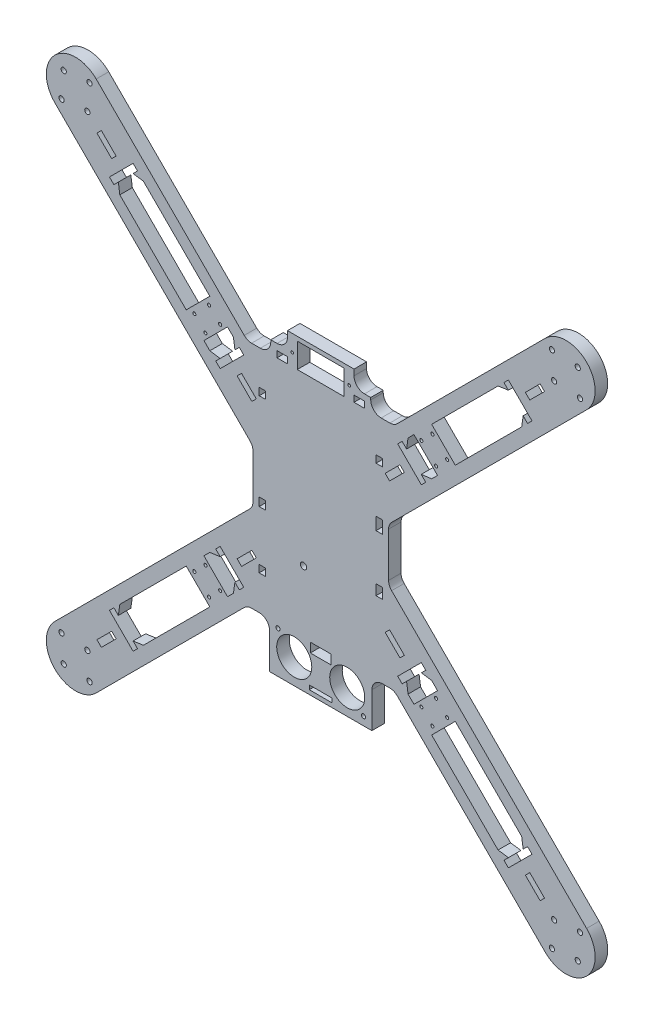
SolidWorks part; units mm, degrees
material "Custom Plastic"
ref_plane "Front Plane" through (0, 0, 0) normal (0, 0, 1) x (1, 0, 0)
ref_plane "Top Plane" through (0, 0, 0) normal (0, 1, 0) x (1, 0, 0)
ref_plane "Right Plane" through (0, 0, 0) normal (1, 0, 0) x (0, 0, -1)
sketch "Sketch1" plane through (0, 0, 0) normal (0, 0, 1) x (1, 0, 0)
  line L0 (117.5, 117.5) -> (-117.5, 117.5) construction
  line L1 (-117.5, 117.5) -> (117.5, -117.5) construction
  line L2 (117.5, -117.5) -> (-117.5, -117.5) construction
  line L3 (-117.5, -117.5) -> (117.5, 117.5) construction
  line L4 (117.5, 117.5) -> (117.5, -117.5) construction
  line L5 (-117.5, 117.5) -> (-117.5, -117.5) construction
  line L6 (0, 117.5) -> (0, -117.5) construction
  line L7 (35.201, 55) -> (15.95, 55)
  line L8 (-32.5, 55) -> (32.5, 55) construction
  line L9 (-35.201, 55) -> (-107.6005, 127.3995)
  line L10 (-127.3995, 107.6005) -> (-32.5, 12.701)
  line L11 (-117.5, 0) -> (117.5, 0) construction
  line L12 (-32.5, 12.701) -> (-32.5, -12.701)
  line L13 (32.5, 55) -> (32.5, -55) construction
  line L14 (32.5, -55) -> (-32.5, -55) construction
  line L15 (-32.5, -55) -> (-32.5, 55) construction
  line L16 (32.5, 55) -> (-32.5, -55) construction
  line L17 (-24.5, -55) -> (-24.5, -77)
  line L18 (-127.3995, -107.6005) -> (-32.5, -12.701)
  line L19 (-24.5, -77) -> (24.5, -77)
  line L20 (-35.201, -55) -> (-107.6005, -127.3995)
  line L21 (35.201, -55) -> (24.5, -55)
  line L22 (35.201, -55) -> (107.6005, -127.3995)
  line L23 (127.3995, -107.6005) -> (32.5, -12.701)
  line L24 (32.5, 12.701) -> (32.5, -12.701)
  line L25 (127.3995, 107.6005) -> (32.5, 12.701)
  line L26 (35.201, 55) -> (107.6005, 127.3995)
  line L27 (24.5, -55) -> (24.5, -77)
  line L28 (-24.5, -55) -> (-35.201, -55)
  line L29 (-15.95, 55) -> (-15.95, 68.8)
  line L30 (-15.95, 68.8) -> (15.95, 68.8)
  line L31 (15.95, 55) -> (15.95, 68.8)
  line L32 (-15.95, 55) -> (-35.201, 55)
  arc A0 (-107.6005, 127.3995) -> (-127.3995, 107.6005) centre (-117.5, 117.5) ccw
  arc A12 (-107.6005, -127.3995) -> (-127.3995, -107.6005) centre (-117.5, -117.5) cw
  arc A16 (107.6005, -127.3995) -> (127.3995, -107.6005) centre (117.5, -117.5) ccw
  arc A24 (107.6005, 127.3995) -> (127.3995, 107.6005) centre (117.5, 117.5) cw
  point P3 (0, 0)
  point P18 (0, 0)
  point P21 (0, -77)
  point P26 (0, 68.8)
  point P33 (-117.5, 117.5)
  point P34 (-32.5, 0)
  point P65 (0, -55)
  point P80 (0, 55)
  dimension "D3" = 14
  dimension "D8" = 24.5
  dimension "D7" = 22
  dimension "D1" = 235
  dimension "D2" = 235
  dimension "D4" = 65
  dimension "D5" = 110
  dimension "D6" = 28
  dimension "D9" = 13.8
  dimension "D10" = 31.9
extrude "Boss-Extrude1" add sketch "Sketch1" against normal blind 6
sketch "Sketch4" plane through (0, 0, 0) normal (0, 0, 1) x (1, 0, 0)
  line L0 (0, 0) -> (0, 55) construction
  line L2 (0, 0) -> (-32.5, 0) construction
  line L3 (-32.5, 12.701) -> (-32.5, -12.701) construction
  line L4 (-32.5, 0) -> (-32.5, 12.701) construction
  line L5 (-32.5, 12.701) -> (-127.3995, 107.6005) construction
  line L6 (-35.201, 55) -> (-107.6005, 127.3995) construction
  line L7 (-107.6005, 127.3995) -> (-127.3995, 107.6005) construction
  line L8 (-110.7825, 124.2175) -> (-124.2175, 110.7825) construction
  line L9 (-123.1569, 123.1569) -> (-111.8431, 111.8431) construction
  circle A20 centre (-110.7825, 124.2175) radius 1.25
  circle A21 centre (-124.2175, 110.7825) radius 1.25
  circle A22 centre (-123.1569, 123.1569) radius 1.25
  circle A23 centre (-111.8431, 111.8431) radius 1.25
  circle A24 centre (111.8431, 111.8431) radius 1.25
  circle A25 centre (110.7825, 124.2175) radius 1.25
  circle A26 centre (123.1569, 123.1569) radius 1.25
  circle A27 centre (124.2175, 110.7825) radius 1.25
  circle A28 centre (111.8431, -111.8431) radius 1.25
  circle A29 centre (124.2175, -110.7825) radius 1.25
  circle A30 centre (123.1569, -123.1569) radius 1.25
  circle A31 centre (110.7825, -124.2175) radius 1.25
  circle A32 centre (-111.8431, -111.8431) radius 1.25
  circle A33 centre (-110.7825, -124.2175) radius 1.25
  circle A34 centre (-123.1569, -123.1569) radius 1.25
  circle A35 centre (-124.2175, -110.7825) radius 1.25
  point P16 (-117.5, 117.5)
  point P19 (-117.5, 117.5)
  point P26 (-117.5, 117.5)
  point P62 (0, 0)
  dimension "D1" = 55
  dimension "D4" = 2.5
  dimension "D2" = 19
  dimension "D5" = 35.201
  dimension "D3" = 16
extrude "Cut-Extrude1" cut sketch "Sketch4" against normal through all
sketch "Sketch5" plane through (0, 0, 0) normal (0, 0, 1) x (1, 0, 0)
  line L4 (0, 0) -> (0, 14.0392) construction
  line L6 (15.95, 68.8) -> (-15.95, 68.8) construction
  line L7 (-11.25, 66.8) -> (-11.25, 55)
  line L8 (-11.25, 55) -> (11.25, 55)
  line L9 (11.25, 55) -> (11.25, 66.8)
  line L10 (11.25, 66.8) -> (-11.25, 66.8)
  line L12 (0, 66.8) -> (0, 55) construction
  line L13 (-13.65, 60.9) -> (13.65, 60.9) construction
  circle A2 centre (-13.65, 60.9) radius 0.65
  circle A3 centre (13.65, 60.9) radius 0.65
  point P20 (0, 60.9)
  point P21 (0, 60.9)
  dimension "D8" = 1.3
  dimension "D9" = 1.3
  dimension "D2" = 2
  dimension "D10" = 27.3
  dimension "D11" = 22.5
  dimension "D12" = 11.8
extrude "Cut-Extrude2" cut sketch "Sketch5" against normal through all
sketch "Sketch6" plane through (0, 0, 0) normal (0, 0, 1) x (1, 0, 0)
  line L1 (-11.25, 55) -> (11.25, 55) construction
  circle A0 centre (-8.25, -25) radius 1.5
  dimension "D3" = 3
  dimension "D1" = 80
  dimension "D2" = 3
extrude "Cut-Extrude3" cut sketch "Sketch6" against normal through all
sketch "Sketch7" plane through (0, 0, 0) normal (0, 0, 1) x (1, 0, 0)
  line L0 (-22.5, -55) -> (-22.5, -75) construction
  line L5 (-22.5, -75) -> (22.5, -75) construction
  line L6 (22.5, -75) -> (22.5, -55) construction
  line L7 (22.5, -55) -> (-22.5, -55) construction
  line L8 (0, -55) -> (0, -75) construction
  line L9 (-12.7, -65) -> (0, -65) construction
  line L10 (-24.5, -77) -> (24.5, -77) construction
  line L11 (-24.5, -55) -> (-24.5, -77) construction
  line L12 (-5, -55) -> (-5, -59.5)
  line L13 (-5, -59.5) -> (5, -59.5)
  line L15 (5, -55) -> (-5, -55)
  line L16 (-5.5, -75) -> (-5.5, -73)
  line L17 (-5.5, -73) -> (5.5, -73)
  line L21 (5.5, -75) -> (-5.5, -75)
  line L22 (5, -55) -> (5, -59.5)
  line L23 (5.5, -75) -> (5.5, -73)
  circle A5 centre (-20.5, -57) radius 1
  circle A6 centre (-12.7, -65) radius 8.4
  circle A7 centre (12.7, -65) radius 8.4
  circle A8 centre (20.5, -73) radius 1
  point P25 (0, -59.5)
  point P26 (0, -73)
  dimension "D3" = 2
  dimension "D6" = 20
  dimension "D13" = 5.5
  dimension "D5" = 45
  dimension "D1" = 2
  dimension "D4" = 16.8
  dimension "D14" = 2
  dimension "D2" = 2
  dimension "D7" = 2
  dimension "D8" = 2
  dimension "D9" = 12.7
  dimension "D10" = 5
  dimension "D11" = 4.5
  dimension "D12" = 2
  dimension "D15" = 2
  dimension "D16" = 2
extrude "Cut-Extrude4" cut sketch "Sketch7" against normal through all
sketch "Sketch8" plane through (0, 0, 0) normal (0, 0, 1) x (1, 0, 0)
  line L0 (101.2365, -89.9228) -> (89.9228, -101.2365)
  line L1 (89.9228, -101.2365) -> (87.8015, -99.1152)
  line L2 (36.8898, -48.2035) -> (48.2035, -36.8898)
  line L3 (48.2035, -36.8898) -> (50.3249, -39.0111)
  line L4 (105.4792, -85.6802) -> (85.6802, -105.4792) construction
  line L5 (127.3995, -107.6005) -> (32.5, -12.701) construction
  line L6 (35.201, -55) -> (107.6005, -127.3995) construction
  line L7 (40.0718, -37.9505) -> (37.9505, -40.0718)
  line L8 (115.8431, -107.8431) -> (111.8431, -111.8431) construction
  line L9 (37.9505, -40.0718) -> (30.8794, -33.0007)
  line L10 (50.3249, 39.0111) -> (48.2035, 36.8898)
  line L11 (30.8794, -33.0007) -> (33.0007, -30.8794)
  line L12 (33.0007, -30.8794) -> (40.0718, -37.9505)
  line L13 (42.5467, -42.5467) -> (39.0111, -39.0111) construction
  line L14 (35.201, -55) -> (107.6005, -127.3995) construction
  line L15 (100.1759, -98.0546) -> (98.0546, -100.1759)
  line L16 (98.0546, -100.1759) -> (105.1256, -107.247)
  line L17 (105.1256, -107.247) -> (107.247, -105.1256)
  line L18 (107.247, -105.1256) -> (100.1759, -98.0546)
  line L19 (99.1152, -99.1152) -> (95.5797, -95.5797) construction
  line L20 (-101.2365, -89.9228) -> (-99.1152, -87.8015)
  line L21 (-100.1759, -98.0546) -> (-107.247, -105.1256)
  line L22 (-107.247, -105.1256) -> (-105.1256, -107.247)
  line L23 (-105.1256, -107.247) -> (-98.0546, -100.1759)
  line L24 (-98.0546, -100.1759) -> (-100.1759, -98.0546)
  line L25 (-89.9228, -101.2365) -> (-101.2365, -89.9228)
  line L26 (-36.8898, -48.2035) -> (-39.0111, -50.3249)
  line L27 (-48.2035, -36.8898) -> (-36.8898, -48.2035)
  line L28 (-37.9505, -40.0718) -> (-40.0718, -37.9505)
  line L29 (-30.8794, -33.0007) -> (-37.9505, -40.0718)
  line L30 (-40.0718, -37.9505) -> (-33.0007, -30.8794)
  line L31 (-33.0007, -30.8794) -> (-30.8794, -33.0007)
  line L32 (-89.9228, 101.2365) -> (-87.8015, 99.1152)
  line L33 (-98.0546, 100.1759) -> (-105.1256, 107.247)
  line L34 (-105.1256, 107.247) -> (-107.247, 105.1256)
  line L35 (-107.247, 105.1256) -> (-100.1759, 98.0546)
  line L36 (-100.1759, 98.0546) -> (-98.0546, 100.1759)
  line L37 (-101.2365, 89.9228) -> (-89.9228, 101.2365)
  line L38 (-48.2035, 36.8898) -> (-50.3249, 39.0111)
  line L39 (-36.8898, 48.2035) -> (-48.2035, 36.8898)
  line L40 (-40.0718, 37.9505) -> (-37.9505, 40.0718)
  line L41 (-33.0007, 30.8794) -> (-40.0718, 37.9505)
  line L42 (-37.9505, 40.0718) -> (-30.8794, 33.0007)
  line L43 (-30.8794, 33.0007) -> (-33.0007, 30.8794)
  line L44 (101.2365, 89.9228) -> (99.1152, 87.8015)
  line L45 (100.1759, 98.0546) -> (107.247, 105.1256)
  line L46 (107.247, 105.1256) -> (105.1256, 107.247)
  line L47 (105.1256, 107.247) -> (98.0546, 100.1759)
  line L48 (98.0546, 100.1759) -> (100.1759, 98.0546)
  line L49 (89.9228, 101.2365) -> (101.2365, 89.9228)
  line L50 (36.8898, 48.2035) -> (39.0111, 50.3249)
  line L51 (48.2035, 36.8898) -> (36.8898, 48.2035)
  line L52 (37.9505, 40.0718) -> (40.0718, 37.9505)
  line L53 (30.8794, 33.0007) -> (37.9505, 40.0718)
  line L54 (40.0718, 37.9505) -> (33.0007, 30.8794)
  line L55 (33.0007, 30.8794) -> (30.8794, 33.0007)
  line L56 (32.5, 12.701) -> (127.3995, 107.6005) construction
  line L57 (41.8396, 53.1533) -> (84.9731, 96.2868)
  line L58 (96.2868, 84.9731) -> (53.1533, 41.8396)
  line L59 (87.8015, 99.1152) -> (89.9228, 101.2365)
  line L60 (99.1152, -87.8015) -> (96.9939, -89.9228)
  line L61 (-96.2868, -84.9731) -> (-53.1533, -41.8396)
  line L62 (96.9939, -89.9228) -> (96.2868, -84.9731)
  line L63 (99.1152, -87.8015) -> (101.2365, -89.9228)
  line L64 (87.8015, -99.1152) -> (89.9228, -96.9939)
  line L65 (-87.8015, -99.1152) -> (-89.9228, -101.2365)
  line L66 (89.9228, -96.9939) -> (84.9731, -96.2868)
  line L67 (84.9731, -96.2868) -> (41.8396, -53.1533)
  line L68 (50.3249, -39.0111) -> (48.2035, -41.1325)
  line L69 (48.2035, -41.1325) -> (53.1533, -41.8396)
  line L70 (53.1533, -41.8396) -> (96.2868, -84.9731)
  line L71 (39.0111, -50.3249) -> (41.1325, -48.2035)
  line L72 (41.1325, -48.2035) -> (41.8396, -53.1533)
  line L73 (39.0111, -50.3249) -> (36.8898, -48.2035)
  line L74 (-89.9228, -96.9939) -> (-84.9731, -96.2868)
  line L75 (-87.8015, -99.1152) -> (-89.9228, -96.9939)
  line L76 (-96.9939, -89.9228) -> (-96.2868, -84.9731)
  line L77 (-99.1152, -87.8015) -> (-96.9939, -89.9228)
  line L78 (-41.1325, -48.2035) -> (-41.8396, -53.1533)
  line L79 (-39.0111, -50.3249) -> (-41.1325, -48.2035)
  line L80 (-48.2035, -41.1325) -> (-53.1533, -41.8396)
  line L81 (-50.3249, -39.0111) -> (-48.2035, -41.1325)
  line L82 (-96.9939, 89.9228) -> (-96.2868, 84.9731)
  line L83 (-99.1152, 87.8015) -> (-96.9939, 89.9228)
  line L84 (-89.9228, 96.9939) -> (-84.9731, 96.2868)
  line L85 (-87.8015, 99.1152) -> (-89.9228, 96.9939)
  line L86 (-48.2035, 41.1325) -> (-53.1533, 41.8396)
  line L87 (-50.3249, 39.0111) -> (-48.2035, 41.1325)
  line L88 (-41.1325, 48.2035) -> (-41.8396, 53.1533)
  line L89 (-39.0111, 50.3249) -> (-41.1325, 48.2035)
  line L90 (89.9228, 96.9939) -> (84.9731, 96.2868)
  line L91 (87.8015, 99.1152) -> (89.9228, 96.9939)
  line L92 (96.9939, 89.9228) -> (96.2868, 84.9731)
  line L93 (99.1152, 87.8015) -> (96.9939, 89.9228)
  line L94 (41.1325, 48.2035) -> (41.8396, 53.1533)
  line L95 (39.0111, 50.3249) -> (41.1325, 48.2035)
  line L96 (48.1429, 41.1931) -> (53.1533, 41.8396)
  line L97 (50.3249, 39.0111) -> (48.1429, 41.1931)
  line L98 (-39.0111, 50.3249) -> (-36.8898, 48.2035)
  line L99 (-53.1533, 41.8396) -> (-96.2868, 84.9731)
  line L100 (-99.1152, 87.8015) -> (-101.2365, 89.9228)
  line L101 (-84.9731, 96.2868) -> (-41.8396, 53.1533)
  line L102 (-41.8396, -53.1533) -> (-84.9731, -96.2868)
  line L103 (-50.3249, -39.0111) -> (-48.2035, -36.8898)
  line L104 (96.2868, 84.9731) -> (84.9731, 96.2868) construction
  line L105 (53.1533, 41.8396) -> (41.8396, 53.1533) construction
  point P10 (95.5797, -95.5797)
  point P11 (95.5797, -95.5797)
  point P18 (-49.2642, 40.0718)
  point P19 (-49.2642, -40.0718)
  point P68 (0, 0)
  point P122 (0, 0)
  dimension "D1" = 23
  dimension "D2" = 75
  dimension "D3" = 3
  dimension "D4" = 10
  dimension "D5" = 5
  dimension "D6" = 6
  dimension "D7" = 3
  dimension "D8" = 10
  dimension "D9" = 5
  dimension "D11" = 6
  dimension "D12" = 3
  dimension "D13" = 4
  dimension "D14" = 3
  dimension "D15" = 3
  dimension "D16" = 4
  dimension "D17" = 3
  dimension "D18" = 3
  dimension "D19" = 4
  dimension "D20" = 3
  dimension "D21" = 3
  dimension "D22" = 4
  dimension "D23" = 3
  dimension "D24" = 3
  dimension "D25" = 4
  dimension "D26" = 3
  dimension "D27" = 4
  dimension "D28" = 3
  dimension "D29" = 3
  dimension "D30" = 4
  dimension "D31" = 4
  dimension "D32" = 3
  dimension "D33" = 3
  dimension "D34" = 4
  dimension "D35" = 4
  dimension "D36" = 3
  dimension "D37" = 3
  dimension "D38" = 4
  dimension "D39" = 4
  dimension "D40" = 3
  dimension "D41" = 3
  dimension "D42" = 4
  dimension "D43" = 4
  dimension "D10" = 4
extrude "Cut-Extrude5" cut sketch "Sketch8" against normal through all
sketch "Sketch9" plane through (-5.6569, 5.6569, 0) normal (0.7071, -0.7071, 0) x (0, 0, -1)
  line L0 (6, 128.1701) -> (6, 67.1701) construction
  line L1 (6, 83.1701) -> (0, 83.1701)
  line L2 (6, 83.1701) -> (6, 71.1701)
  line L3 (6, 71.1701) -> (0, 71.1701)
  line L4 (0, 83.1701) -> (0, 71.1701)
  line L5 (0, 128.1701) -> (0, 67.1701) construction
  line L6 (0, 0) -> (28.0274, 0) construction
  line L7 (6, 63.1701) -> (0, 63.1701) construction
  dimension "D1" = 8
  dimension "D2" = 12
extrude "Boss-Extrude2" add sketch "Sketch9" along normal up to next
sketch "Sketch11" plane through (5.6569, 5.6569, 0) normal (-0.7071, -0.7071, 0) x (0, 0, 1)
  line L0 (-6, -128.1701) -> (-6, -67.1701) construction
  line L1 (-6, -71.1701) -> (0, -71.1701)
  line L2 (-6, -71.1701) -> (-6, -83.1701)
  line L3 (-6, -83.1701) -> (0, -83.1701)
  line L4 (0, -71.1701) -> (0, -83.1701)
  line L5 (0, -128.1701) -> (0, -67.1701) construction
  line L6 (-6, -63.1701) -> (0, -63.1701) construction
  dimension "D1" = 8
  dimension "D2" = 12
extrude "Boss-Extrude3" add sketch "Sketch11" along normal up to next
sketch "Sketch12" plane through (5.6569, -5.6569, 0) normal (-0.7071, 0.7071, 0) x (0, 0, 1)
  line L0 (-6, -128.1701) -> (-6, -67.1701) construction
  line L1 (-6, -71.1701) -> (0, -71.1701)
  line L2 (-6, -71.1701) -> (-6, -83.1701)
  line L3 (-6, -83.1701) -> (0, -83.1701)
  line L4 (0, -71.1701) -> (0, -83.1701)
  line L5 (0, -128.1701) -> (0, -67.1701) construction
  dimension "D1" = 8
  dimension "D2" = 12
extrude "Boss-Extrude4" add sketch "Sketch12" along normal up to next
sketch "Sketch13" plane through (5.6569, 5.6569, 0) normal (-0.7071, -0.7071, 0) x (0, 0, 1)
  line L0 (-6, 67.1701) -> (-6, 128.1701) construction
  line L1 (-6, 71.1701) -> (0, 71.1701)
  line L2 (-6, 71.1701) -> (-6, 83.1701)
  line L3 (-6, 83.1701) -> (0, 83.1701)
  line L4 (0, 71.1701) -> (0, 83.1701)
  line L5 (0, 67.1701) -> (0, 128.1701) construction
  dimension "D1" = 8
  dimension "D2" = 12
extrude "Boss-Extrude5" add sketch "Sketch13" along normal up to next
sketch "Sketch14" plane through (0, 0, -6) normal (0, 0, -1) x (-1, 0, 0)
  line L0 (32.5, 0) -> (-32.5, 0) construction
  line L1 (32.5, 12.701) -> (32.5, -12.701) construction
  line L2 (-32.5, -12.701) -> (-32.5, 12.701) construction
  line L3 (28, -38.5) -> (28, 38.5) construction
  line L14 (-26.5, 13) -> (-26.5, 7)
  line L17 (-26.5, 7) -> (-29.5, 7)
  line L19 (-26.5, 13) -> (-29.5, 13)
  line L23 (26.5, -38.5) -> (29.5, -38.5)
  line L24 (26.5, -38.5) -> (26.5, -35)
  line L25 (26.5, -35) -> (29.5, -35)
  line L26 (29.5, -38.5) -> (29.5, -35)
  line L27 (26.5, -11) -> (29.5, -11)
  line L28 (26.5, -11) -> (26.5, -7)
  line L29 (26.5, -7) -> (29.5, -7)
  line L30 (29.5, -11) -> (29.5, -7)
  line L31 (26.5, 35) -> (29.5, 35)
  line L32 (26.5, 35) -> (26.5, 38.5)
  line L33 (26.5, 38.5) -> (29.5, 38.5)
  line L34 (29.5, 35) -> (29.5, 38.5)
  line L35 (-29.5, 13) -> (-29.5, 7)
  line L36 (32.5, 12.701) -> (32.5, -12.701) construction
  line L37 (-26.5, -20) -> (-29.5, -20)
  line L38 (-26.5, -20) -> (-26.5, -15)
  line L39 (-26.5, -15) -> (-29.5, -15)
  line L40 (-29.5, -20) -> (-29.5, -15)
  line L41 (-26.5, 35) -> (-29.5, 35)
  line L42 (-26.5, 35) -> (-26.5, 38.5)
  line L43 (-26.5, 38.5) -> (-29.5, 38.5)
  line L44 (-29.5, 35) -> (-29.5, 38.5)
  line L45 (-32.5, -12.701) -> (-32.5, 12.701) construction
  point P11 (28, -38.5)
  point P16 (28, 0)
  point P28 (-28, 13)
  point P38 (-28, 7)
  dimension "D2" = 3
  dimension "D3" = 3.5
  dimension "D4" = 24
  dimension "D5" = 7
  dimension "D6" = 22
  dimension "D7" = 6
  dimension "D8" = 3.5
  dimension "D9" = 22
  dimension "D10" = 4
  dimension "D11" = 3.5
  dimension "D12" = 42
  dimension "D13" = 5
  dimension "D14" = 3
  dimension "D15" = 3
  dimension "D16" = 3
  dimension "D17" = 7
extrude "Cut-Extrude6" cut sketch "Sketch14" against normal through all
sketch "Sketch15" plane through (0, 0, -6) normal (0, 0, -1) x (-1, 0, 0)
  line L0 (-55.2746, -48.2035) -> (-48.2035, -55.2746) construction
  line L1 (-48.2035, -55.2746) -> (-53.5068, -60.5779) construction
  line L2 (-53.5068, -60.5779) -> (-60.5779, -53.5068) construction
  line L3 (-60.5779, -53.5068) -> (-55.2746, -48.2035) construction
  line L4 (-64.2902, -44.4912) -> (-44.4912, -64.2902) construction
  line L5 (-127.3995, -107.6005) -> (-32.5, -12.701) construction
  line L6 (-35.201, -55) -> (-107.6005, -127.3995) construction
  line L7 (-57.0424, -57.0424) -> (-51.7391, -51.7391) construction
  line L8 (-53.1533, -64.467) -> (-64.467, -53.1533) construction
  circle A6 centre (-60.5779, -53.5068) radius 0.75
  circle A7 centre (-55.2746, -48.2035) radius 0.75
  circle A8 centre (-48.2035, -55.2746) radius 0.75
  circle A9 centre (-53.5068, -60.5779) radius 0.75
  circle A10 centre (-53.5068, 60.5779) radius 0.75
  circle A11 centre (-48.2035, 55.2746) radius 0.75
  circle A12 centre (-60.5779, 53.5068) radius 0.75
  circle A13 centre (-55.2746, 48.2035) radius 0.75
  circle A14 centre (60.5779, 53.5068) radius 0.75
  circle A15 centre (55.2746, 48.2035) radius 0.75
  circle A16 centre (53.5068, 60.5779) radius 0.75
  circle A17 centre (48.2035, 55.2746) radius 0.75
  circle A18 centre (53.5068, -60.5779) radius 0.75
  circle A19 centre (48.2035, -55.2746) radius 0.75
  circle A20 centre (60.5779, -53.5068) radius 0.75
  circle A21 centre (55.2746, -48.2035) radius 0.75
  point P12 (-54.3907, -54.3907)
  point P19 (-54.3907, -54.3907)
  point P47 (0, 0)
  dimension "D3" = 1.5
  dimension "D1" = 7.5
  dimension "D2" = 10
  dimension "D4" = 2.5
  dimension "D5" = 4
extrude "Cut-Extrude7" cut sketch "Sketch15" against normal through all
sketch "Sketch17" plane through (0, 0, -6) normal (0, 0, -1) x (-1, 0, 0)
  line L0 (0, 68.8) -> (0, 41.1241) construction
  line L1 (15.95, 55) -> (23.95, 55)
  line L2 (15.95, 55) -> (15.95, 61)
  line L3 (15.95, 61) -> (23.95, 61)
  line L4 (23.95, 55) -> (23.95, 61)
  line L5 (-15.95, 68.8) -> (15.95, 68.8) construction
  line L6 (-15.95, 55) -> (-15.95, 58)
  line L7 (20.95, 55) -> (15.95, 55)
  line L10 (15.95, 55) -> (15.95, 58)
  line L11 (-20.95, 58) -> (-15.95, 58)
  line L12 (-20.95, 55) -> (-20.95, 58)
  line L13 (-20.95, 55) -> (-15.95, 55)
  line L14 (-23.95, 55) -> (-23.95, 61)
  line L15 (-15.95, 61) -> (-23.95, 61)
  line L16 (-15.95, 55) -> (-15.95, 61)
  line L17 (-15.95, 55) -> (-23.95, 55)
  dimension "D1" = 6
  dimension "D2" = 8
extrude "Boss-Extrude8" add sketch "Sketch17" against normal up to surface (6 mm away) contours L2 L3 L4 L1 | L16 L15 L14 L17 up to face at (47.4535, 55.2746, 0)
sketch "Sketch19" plane through (0, 0, -6) normal (0, 0, -1) x (-1, 0, 0)
  line L0 (15.95, 61) -> (23.95, 61) construction
  line L1 (20.95, 58) -> (15.95, 58)
  line L2 (20.95, 58) -> (20.95, 55)
  line L3 (20.95, 55) -> (15.95, 55)
  line L4 (15.95, 58) -> (15.95, 55)
  line L5 (23.95, 55) -> (23.95, 61) construction
  line L6 (0, 68.8) -> (0, 43.8944) construction
  line L7 (-15.95, 68.8) -> (15.95, 68.8) construction
  line L8 (-15.95, 58) -> (-15.95, 55)
  line L9 (-20.95, 55) -> (-15.95, 55)
  line L10 (-20.95, 58) -> (-20.95, 55)
  line L11 (-20.95, 58) -> (-15.95, 58)
  dimension "D1" = 5
  dimension "D2" = 3
  dimension "D3" = 3
  dimension "D4" = 3
extrude "Cut-Extrude9" cut sketch "Sketch19" against normal through all
fillet "Fillet1" radius 5 14 edges at (-32.5, -12.701, -3) (-32.5, 12.701, -3) (32.5, 12.701, -3) (32.5, -12.701, -3) (24.5, -55, -3) (35.201, -55, -3) (-24.5, -55, -3) (-35.201, -55, -3) (15.95, 61, -3) (23.95, 55, -3) (35.201, 55, -3) (-15.95, 61, -3) (-23.95, 55, -3) (-35.201, 55, -3)
